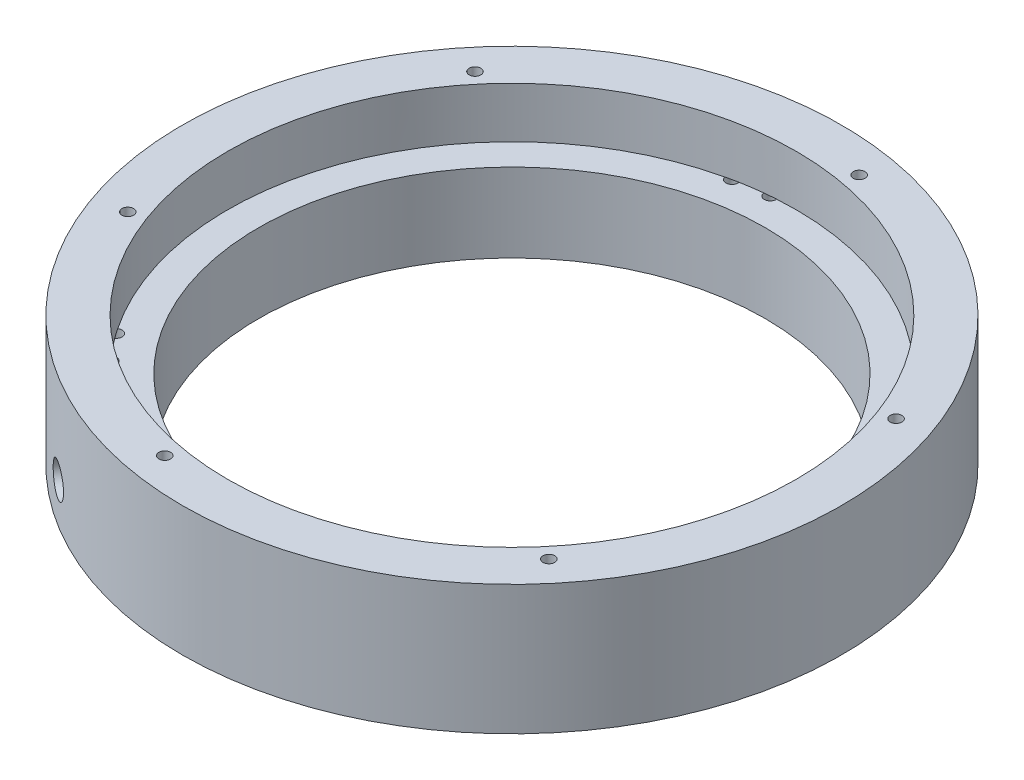
SolidWorks part; units mm, degrees
material "6061 Alloy"
ref_plane "Front Plane" through (0, 0, 0) normal (0, 0, 1) x (1, 0, 0)
ref_plane "Top Plane" through (0, 0, 0) normal (0, 1, 0) x (1, 0, 0)
ref_plane "Right Plane" through (0, 0, 0) normal (1, 0, 0) x (0, 0, -1)
sketch "Sketch1" plane through (0, 0, 0) normal (0, 1, 0) x (1, 0, 0)
  line L0 (26.7963, -63.1282) -> (0, 0) construction
  line L1 (0, 0) -> (0, -32.7983) construction
  line L2 (0, 0) -> (58.126, -27.1046) construction
  line L3 (0, 0) -> (-15.1655, -86.0079) construction
  line L4 (0, 0) -> (84.7676, -52.9687) construction
  circle A0 centre (0, 0) radius 57.15
  circle A1 centre (0, 0) radius 74.3712
  circle A3 centre (0, 0) radius 64.135
  circle A4 centre (-11.7434, -66.6001) radius 1.3208
  circle A5 centre (26.7963, -63.1282) radius 1.9939
  circle A6 centre (26.7963, -63.1282) radius 5.3277
  circle A7 centre (58.126, -27.1046) radius 1.3589
  circle A8 centre (60.9305, -20.0194) radius 1.3589
  dimension "D1" = 114.3
  dimension "D5" = 2.6416
  dimension "D7" = 3.9878
  dimension "D9" = 10.6553
  dimension "D10" = 2.7178
  dimension "D2" = 148.7424
  dimension "D4" = 67.6275
  dimension "D6" = 68.58
  dimension "D8" = 23
  dimension "D11" = 65
  dimension "D15" = 58
  dimension "D12" = 7.62
  dimension "D13" = 10
  dimension "D3" = 6.985
extrude "Boss-Extrude1" add sketch "Sketch1" along normal blind 17.78 contours A7 A3 A6 A0 | A3 A6 A5 | A5 | A3 A6 | A1 A7 A3 A6 A4 | A3 A7 | A3 A7 | A3 A8 | A3 A8 region at (-72.2677, 0, 0) region at (61.6385, 0, 9.1979) region at (24.9157, 0, 58.6977) region at (25.1182, 0, 59.1748) region at (61.4759, 0, 20.1987) region at (60.3801, 0, 19.8386) region at (57.601, 0, 26.8598) region at (58.6464, 0, 27.3473) region at (26.7963, 0, 63.1282)
extrude "Boss-Extrude3" add sketch "Sketch1<3>" along normal blind 11.43 from surface contours A1 A7 A3 A6 A4 | A3 A6 A5 | A5 | A3 A7 | A3 A8 region at (-72.2677, 0, 0) region at (25.1182, 0, 59.1748) region at (61.4759, 0, 20.1987) region at (58.6464, 0, 27.3473) region at (26.7963, 0, 63.1282) starting at face at (0, 17.78, 57.15)
sketch "Sketch1<3>" plane through (0, 0, 0) normal (0, 1, 0) x (1, 0, 0) same geometry as "Sketch1"
pattern_circular "CirPattern1" count 6 over 360 about axis through (0, 29.21, 0) along (0, 1, 0) of face at (-11.7434, 0, 67.9209)
sketch "Sketch2" plane through (0, 0, 0) normal (1, 0, 0) x (0, 0, -1)
  line L0 (-57.15, 0) -> (57.15, 0) construction
  line L1 (57.15, 17.78) -> (-57.15, 17.78) construction
  line L2 (-57.15, 0) -> (57.15, 0)
  line L3 (57.15, 17.78) -> (-57.15, 17.78)
  line L4 (91.6697, 17.018) -> (97.1828, 17.018) construction
  line L5 (0, 17.78) -> (0, 35.8369)
  circle A0 centre (60.6425, 18.6055) radius 1.5875 construction
  circle A1 centre (60.6425, 18.669) radius 1.651
  dimension "D2" = 3.175
  dimension "D4" = 3.302
  dimension "D1" = 60.6425
  dimension "D3" = 0.762
extrude "Cut-Extrude2" cut sketch "Sketch1<4>" along normal blind 5.08 contours A3 A6 A5 | A3 A6 | A6 region at (24.9157, 0, 58.6977) region at (25.1182, 0, 59.1748)
sketch "Sketch1<4>" plane through (0, 0, 0) normal (0, 1, 0) x (1, 0, 0) same geometry as "Sketch1"
extrude "Cut-Extrude3" cut sketch "Sketch1<5>" along normal blind 6.35 contours A5 region at (26.7963, 0, 63.1282)
sketch "Sketch1<5>" plane through (0, 0, 0) normal (0, 1, 0) x (1, 0, 0) same geometry as "Sketch1"
pattern_circular "CirPattern3" count 3 over 360 about axis through (0, 0, 0) along (0, 1, 0) of face at (26.7963, 6.35, 65.1221) of face at (26.7963, 6.35, 65.1221) of face at (26.7963, 5.08, 65.1221) of face at (26.7963, 5.08, 68.4559)
ref_plane "Plane1" through (0, 0, 0) normal (-0.5299, 0, 0.848) x (0.848, 0, 0.5299)
sketch "Sketch3" plane through (0, 0, 0) normal (-0.5299, 0, 0.848) x (0.848, 0, 0.5299)
  line L0 (57.15, 17.78) -> (-57.15, 17.78) construction
  line L1 (57.15, 17.78) -> (-57.15, 17.78)
  line L2 (0, 0) -> (0, 17.78) construction
  circle A0 centre (0, 8.89) radius 3.6576
  circle A1 centre (0, 8.89) radius 3.9751
  dimension "D1" = 7.3152
  dimension "D3" = 7.9502
  dimension "D2" = 8.89
extrude "Cut-Extrude5" cut sketch "Sketch3" along normal up to surface (74.2812 mm away) contours L2 A0 | A0 L2 region at (-1.3165, 8.89, -0.8226) region at (1.3165, 8.89, 0.8226) up to face at (0, 0, 74.3712)
extrude "Cut-Extrude13" cut sketch "Sketch1<6>" along normal up to surface (17.78 mm away) contours A3 A8 | A3 A8 | A7 region at (61.4759, 0, 20.1987) region at (60.3801, 0, 19.8386) up to face at (0, 17.78, 57.15)
sketch "Sketch1<6>" plane through (0, 0, 0) normal (0, 1, 0) x (1, 0, 0) same geometry as "Sketch1"
pattern_circular "CirPattern4" count 3 over 360 about axis through (0, 0, 0) along (0, 1, 0) of "Cut-Extrude13"
equation "\"Middle Coupler Inner Daimeter\"= 3.875in"
equation "\"Middle Coupler  Wall Thickness\" = 0.25in"
equation "\"Middle Coupler Bottom Thickness\"= 0.2in"
equation "\"Bearing Rail Offset\"= 0.45in"
equation "\"3-56 UNF Tap\"= 0.089in"
equation "\"3-56 UNF Clearance\"= 0.104in"
equation "\"Ball Bearing Distance\"= 0.03in"
equation "\"D1@Sketch1\"=\"Middle Coupler Inner Daimeter\"+0.625in"
equation "\"D3@Sketch1\"=0.275"
equation "\"D4@Sketch1\"=\"Middle Coupler Inner Daimeter\"/2+0.625/2+0.275+0.275/2"
equation "\"D5@Sketch1\"=\"3-48 Clearance\""
equation "\"D1@Sketch2\"=\"Middle Coupler Inner Daimeter\"/2in + \"Bearing Rail Offset\""
equation "\"D3@Sketch2\"=\"Ball Bearing Distance\""
equation "\"D4@Sketch2\"=\"D2@Sketch2\"+0.005"
equation "\"D1@Boss-Extrude3\"=0.320in+0.01in + 0.03*4"
equation "\"TCA Outer Diameter\" = 6in"
equation "\"Interstage Aeroframe Wall Thickness\" = 0.072in"
equation "\"Compression Spring OD\"= 0.42in"
equation "\"10-24 Tap\"= 0.157in"
equation "\"10-24 Clearance\"= 0.196in"
equation "\"Lower Stage Fuselage Wall Thickness\" = 0.25in"
equation "\"6-32 Tap\" = 0.107in"
equation "\"D10@Sketch1\"=\"6-32 Tap\""
equation "\"1/4-20 Tap\" = 0.201in"
equation "\"D1@Sketch3\"=0.176 + 0.056*2"
equation "\"12-24 Tap\" = 0.177in"
equation "\"D3@Sketch3\"=0.313"
equation "\"3-48 Tap\"= 0.079in"
equation "\"3-48 Clearance\" = 0.104in"
equation "\"6-32 Clearance\" = 0.144"
equation "\"D2@Sketch1\"=\"TCA Outer Diameter\"-\"Interstage Aeroframe Wall Thickness\"*2"
equation "\"D6@Sketch1\"=(\"Middle Coupler Inner Daimeter\"+\"TCA Outer Diameter\"+0.5+0.0125*2in)/4 + 0.1"
